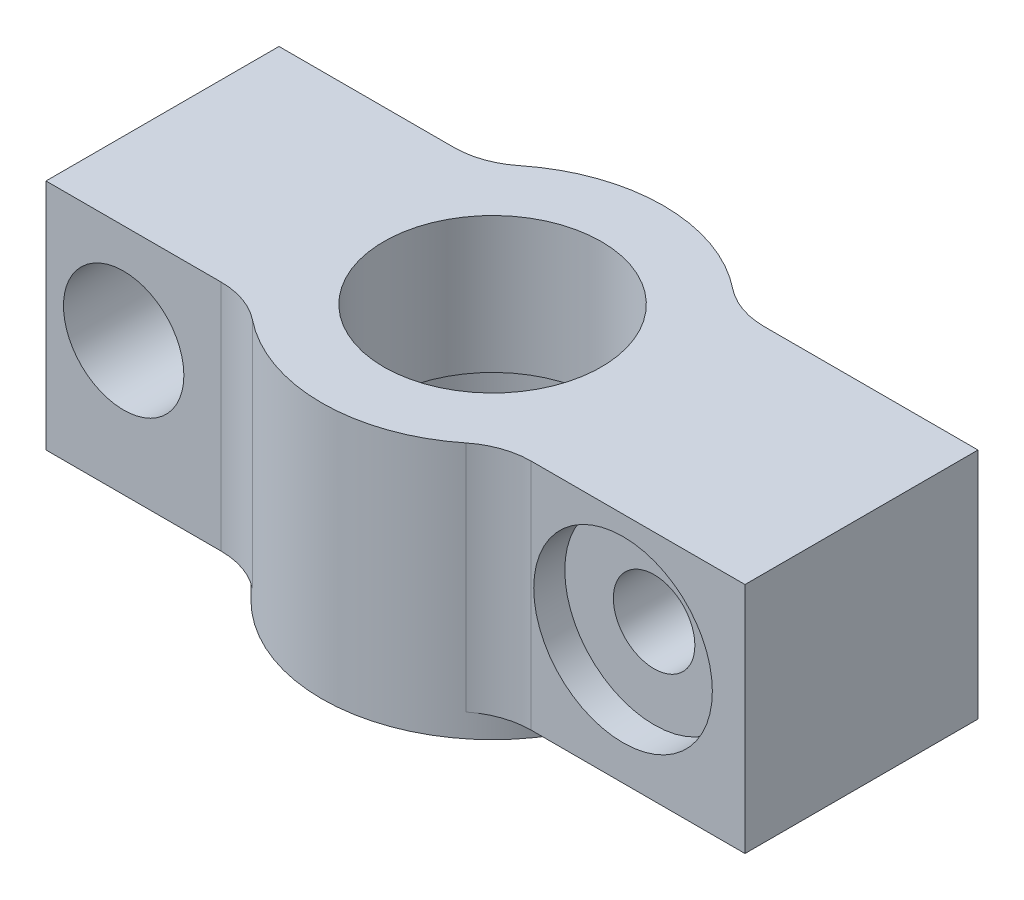
SolidWorks part; units mm, degrees
ref_plane "Front Plane" through (0, 0, 0) normal (0, 0, 1) x (1, 0, 0)
ref_plane "Top Plane" through (0, 0, 0) normal (0, 1, 0) x (1, 0, 0)
ref_plane "Right Plane" through (0, 0, 0) normal (1, 0, 0) x (0, 0, -1)
sketch "Sketch1" plane through (0, 0, 0) normal (0, 1, 0) x (1, 0, 0)
  line L0 (16.0935, 15) -> (47.5, 15)
  line L1 (-47.5, 15) -> (-16.0935, 15)
  line L2 (-47.5, 15) -> (-47.5, -15)
  line L3 (-47.5, -15) -> (-16.0935, -15)
  line L4 (47.5, 15) -> (47.5, -15)
  line L5 (16.0935, -15) -> (47.5, -15)
  arc A0 (-16.0935, -15) -> (16.0935, -15) centre (0, 0) ccw
  arc A1 (16.0935, 15) -> (-16.0935, 15) centre (0, 0) ccw
  point P0 (0, 0)
  dimension "D3" = 44
  dimension "D1" = 95
  dimension "D2" = 30
extrude "Boss-Extrude2" add sketch "Sketch1" along normal blind 3
sketch "Sketch3" plane through (0, 3, 0) normal (0, 1, 0) x (1, 0, 0)
  line L0 (-16.0935, 15) -> (-47.5, 15) construction
  line L1 (-42.5, 15) -> (-22.5, 15)
  line L2 (-42.5, 15) -> (-42.5, -15)
  line L3 (-42.5, -15) -> (-22.5, -15)
  line L4 (-22.5, 15) -> (-22.5, -15)
  line L5 (-47.5, -15) -> (-16.0935, -15) construction
  line L6 (-47.5, 15) -> (-47.5, -15) construction
  dimension "D1" = 20
  dimension "D2" = 5
extrude "Boss-Extrude5" add sketch "Sketch3" along normal blind 26
sketch "Sketch8" plane through (0, 0, 15) normal (0, 0, 1) x (1, 0, 0)
  line L0 (-42.5, 29) -> (-22.5, 29) construction
  circle A0 centre (-32.5, 17.2) radius 7.75
  dimension "D1" = 15.5
  dimension "D2" = 11.8
extrude "Cut-Extrude2" cut sketch "Sketch8" against normal blind 36
sketch "Sketch9" plane through (0, 3, 0) normal (0, 1, 0) x (1, 0, 0)
  line L0 (16.0935, 15) -> (47.5, 15)
  line L1 (47.5, 15) -> (47.5, -15)
  line L2 (47.5, -15) -> (16.0935, -15)
  arc A1 (16.0935, 15) -> (16.0935, -15) centre (0, 0) cw
extrude "Boss-Extrude7" add sketch "Sketch9" along normal blind 27
sketch "Sketch14" plane through (0, 3, 0) normal (0, 1, 0) x (1, 0, 0)
  circle A0 centre (0, 0) radius 22
extrude "Boss-Extrude8" add sketch "Sketch14" along normal blind 20
sketch "Sketch16" plane through (0, 0, 15) normal (0, 0, 1) x (1, 0, 0)
  line L0 (16.0935, 30) -> (47.5, 30) construction
  circle A0 centre (31.7967, 16) radius 11.5
  dimension "D1" = 23
  dimension "D2" = 14
extrude "Cut-Extrude3" cut sketch "Sketch16" against normal blind 4
sketch "Sketch17" plane through (0, 0, 11) normal (0, 0, 1) x (1, 0, 0)
  circle A0 centre (31.7967, 16) radius 5.25
  dimension "D1" = 10.5
extrude "Cut-Extrude4" cut sketch "Sketch17" against normal blind 44
sketch "Sketch18" plane through (0, 0, -15) normal (0, 0, -1) x (-1, 0, 0)
  circle A0 centre (-31.7967, 16) radius 11.5
  dimension "D1" = 23
extrude "Cut-Extrude5" cut sketch "Sketch18" against normal blind 4
sketch "Sketch19" plane through (0, 0, 0) normal (0, -1, 0) x (1, 0, 0)
  circle A0 centre (0, 0) radius 16.9
  point P3 (0, 0)
  dimension "D1" = 33.8
sketch "Sketch24" plane through (0, 23, 0) normal (0, 1, 0) x (1, 0, 0)
  line L0 (0, 0) -> (35.8498, 0) construction
  line L2 (21.3498, 2) -> (14.5, 2)
  line L3 (21.3498, 2) -> (21.3498, -2)
  line L4 (21.3498, -2) -> (14.5, -2)
  line L5 (14.5, 2) -> (14.5, -2)
  line L6 (21.3498, 2) -> (14.5, -2) construction
  line L7 (21.3498, -2) -> (14.5, 2) construction
  point P3 (17.9249, 0)
  dimension "D1" = 4
extrude "Boss-Extrude12" add sketch "Sketch24" against normal blind 13
sketch "Sketch25" plane through (0, 0, 15) normal (0, 0, 1) x (1, 0, 0)
  line L0 (-22, 23) -> (-22, 3) construction
  line L1 (-22.5, 3) -> (-22, 3)
  line L2 (-22.5, 3) -> (-22.5, 19.8967)
  line L3 (-22.5, 19.8967) -> (-22, 19.8967)
  line L4 (-22, 3) -> (-22, 19.8967)
sketch "Sketch26" plane through (0, 3, 0) normal (0, 1, 0) x (1, 0, 0)
  line L0 (-42.5, 15) -> (-42.5, -15) construction
  line L1 (-47.5, 15) -> (-42.5, 15)
  line L2 (-47.5, 15) -> (-47.5, -15)
  line L3 (-47.5, -15) -> (-42.5, -15)
  line L4 (-42.5, 15) -> (-42.5, -15)
extrude "Cut-Extrude10" cut sketch "Sketch26" against normal blind 6
sketch "Sketch27" plane through (0, 23, 0) normal (0, 1, 0) x (1, 0, 0)
  circle A0 centre (0, 0) radius 22
extrude "Boss-Extrude15" add sketch "Sketch27" along normal blind 7
sketch "Sketch36" plane through (0, 3, 0) normal (0, 1, 0) x (1, 0, 0)
  line L0 (-16.0935, -15) -> (-22.5, -15)
  line L1 (-22.5, -15) -> (-22.5, 15)
  line L2 (-22.5, 15) -> (-16.0935, 15)
  arc A0 (-16.0935, 15) -> (-16.0935, -15) centre (0, 0) ccw
extrude "Boss-Extrude17" add sketch "Sketch36" along normal blind 27
sketch "Sketch37" plane through (0, 29, 0) normal (0, 1, 0) x (1, 0, 0)
  line L1 (-42.5, 15) -> (-22.5, 15)
  line L2 (-42.5, 15) -> (-42.5, -15)
  line L3 (-42.5, -15) -> (-22.5, -15)
  line L4 (-22.5, 15) -> (-22.5, -15)
extrude "Boss-Extrude18" add sketch "Sketch37" along normal blind 1
fillet "Fillet17" radius 10 4 edges at (16.0935, 15, -15) (-16.0935, 15, -15) (-16.0935, 15, 15) (16.0935, 15, 15)
sketch "Sketch39" plane through (0, 0, 0) normal (0, -1, 0) x (1, 0, 0)
  circle A0 centre (0, 0) radius 22
sketch "Sketch41" plane through (0, 0, 0) normal (0, -1, 0) x (1, 0, 0)
  circle A0 centre (0, 0) radius 22
extrude "Boss-Extrude19" add sketch "Sketch41" along normal blind 3
sketch "Sketch42" plane through (0, -3, 0) normal (0, -1, 0) x (1, 0, 0)
  circle A0 centre (0, 0) radius 16.9
sketch "Sketch44" plane through (0, 30, 0) normal (0, 1, 0) x (1, 0, 0)
  line L0 (0, 0) -> (47.5, 0) construction
  line L1 (47.5, -15) -> (47.5, 15) construction
  line L3 (13.9785, 2) -> (19.8215, 2)
  line L4 (13.9785, 2) -> (13.9785, -2)
  line L5 (13.9785, -2) -> (19.8215, -2)
  line L6 (19.8215, 2) -> (19.8215, -2)
  line L7 (13.9785, 2) -> (19.8215, -2) construction
  line L8 (13.9785, -2) -> (19.8215, 2) construction
  circle A0 centre (0, 0) radius 16.9 construction
  point P5 (16.9, 0)
  dimension "D1" = 4
extrude "Boss-Extrude21" add sketch "Sketch44" against normal blind 22
sketch "Sketch46" plane through (0, -3, 0) normal (0, -1, 0) x (1, 0, 0)
  circle A0 centre (0, 0) radius 16.9
extrude "Cut-Extrude11" cut sketch "Sketch46" against normal blind 15.5
sketch "Sketch48" plane through (0, 12.5, 0) normal (0, -1, 0) x (1, 0, 0)
  circle A0 centre (0, 0) radius 14
  dimension "D1" = 28
extrude "Cut-Extrude13" cut sketch "Sketch48" against normal blind 25.5
sketch "Sketch49" plane through (0, 30, 0) normal (0, 1, 0) x (1, 0, 0)
  line L0 (0, 0) -> (47.5, 0) construction
  line L1 (47.5, -15) -> (47.5, 15) construction
  line L3 (14.03, 2.5) -> (19.3516, 2.5)
  line L4 (14.03, 2.5) -> (14.03, -2.5)
  line L5 (14.03, -2.5) -> (19.3516, -2.5)
  line L6 (19.3516, 2.5) -> (19.3516, -2.5)
  line L7 (14.03, 2.5) -> (19.3516, -2.5) construction
  line L8 (14.03, -2.5) -> (19.3516, 2.5) construction
  point P5 (16.6908, 0)
  dimension "D1" = 5
extrude "Boss-Extrude24" add sketch "Sketch49" against normal blind 20
